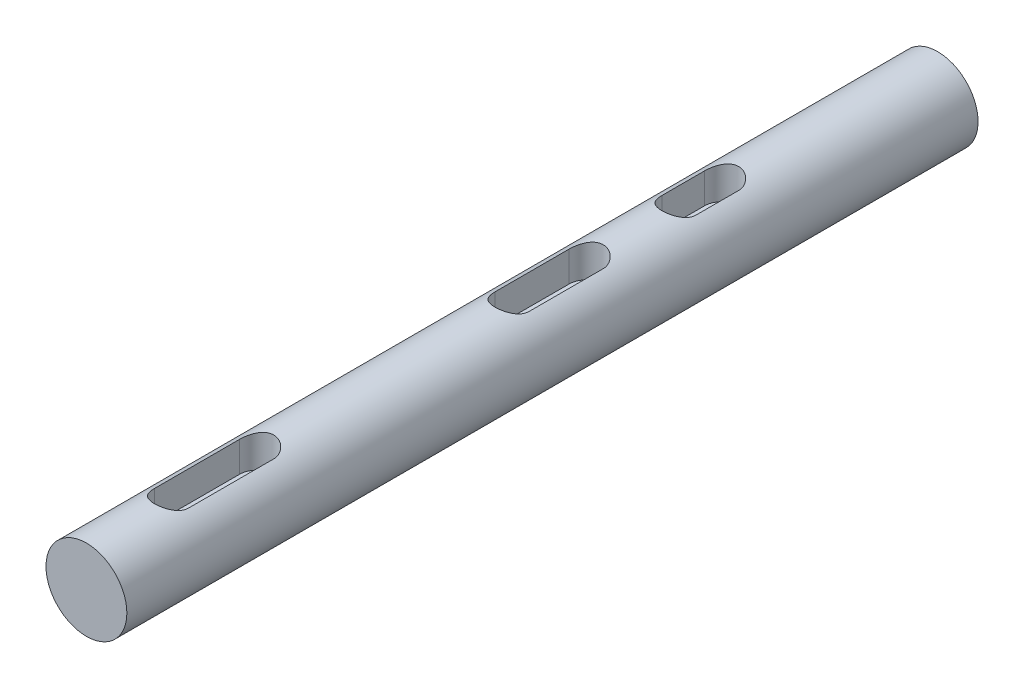
SolidWorks part; units mm, degrees
ref_plane "Front Plane" through (0, 0, 0) normal (0, 0, 1) x (1, 0, 0)
ref_plane "Top Plane" through (0, 0, 0) normal (0, 1, 0) x (1, 0, 0)
ref_plane "Right Plane" through (0, 0, 0) normal (1, 0, 0) x (0, 0, -1)
sketch "Sketch1" plane through (0, 0, 0) normal (0, 0, 1) x (1, 0, 0)
  circle A0 centre (0, 0) radius 4.75
  dimension "D1" = 9.5
extrude "Boss-Extrude1" add sketch "Sketch1" along normal blind 0.0001
sketch "Sketch4" plane through (0, 0, 0) normal (0, 0, -1) x (-1, 0, 0)
  circle A0 centre (0, 0) radius 4.75
  dimension "D1" = 9.5
extrude "Boss-Extrude2" add sketch "Sketch4" along normal blind 105
ref_axis "Axis1" through (0, 0, -132.4687) along (0, 0, 1)
ref_plane "Plane1" through (0, 4.75, 0) normal (0, 1, 0) x (1, 0, 0)
sketch "Sketch5" plane through (0, 4.75, 0) normal (0, 1, 0) x (1, 0, 0)
  line L0 (0, -4.3175) -> (0, 99.6122) construction
  line L1 (0, 10) -> (0, 20) construction
  line L2 (-2, 10) -> (-2, 20)
  line L3 (2, 10) -> (2, 20)
  line L4 (0, 50) -> (0, 58.71) construction
  line L5 (-2, 50) -> (-2, 58.71)
  line L6 (2, 50) -> (2, 58.71)
  line L11 (0, 69.62) -> (0, 74.62) construction
  line L12 (-2, 69.62) -> (-2, 74.62)
  line L13 (2, 69.62) -> (2, 74.62)
  arc A0 (-2, 10) -> (2, 10) centre (0, 10) ccw
  arc A1 (2, 20) -> (-2, 20) centre (0, 20) ccw
  arc A2 (-2, 50) -> (2, 50) centre (0, 50) ccw
  arc A3 (2, 58.71) -> (-2, 58.71) centre (0, 58.71) ccw
  arc A6 (-2, 69.62) -> (2, 69.62) centre (0, 69.62) ccw
  arc A7 (2, 74.62) -> (-2, 74.62) centre (0, 74.62) ccw
  point P5 (0, 15)
  point P10 (0, 54.355)
  point P28 (0, 72.12)
  dimension "D1" = 10
  dimension "D2" = 4
  dimension "D3" = 4
  dimension "D4" = 49.62
  dimension "D5" = 8.71
  dimension "D8" = 30
  dimension "D11" = 2.5
  dimension "D12" = 4
extrude "Cut-Extrude3" cut sketch "Sketch5" against normal blind 4
sketch "Sketch6" plane through (0, 0, -105) normal (0, 0, -1) x (-1, 0, 0)
  circle A0 centre (0, 0) radius 4.75
extrude "Cut-Extrude4" cut sketch "Sketch6" against normal blind 5
